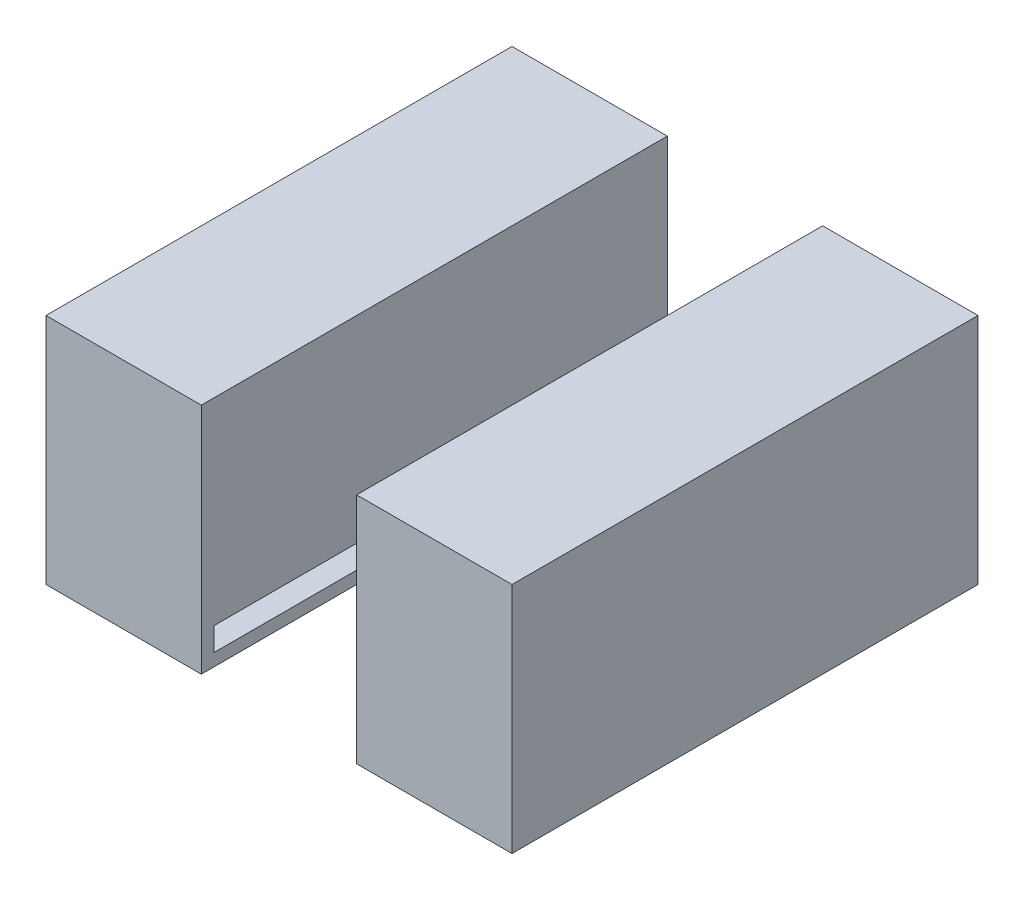
SolidWorks part; units mm, degrees
material "ABS"
ref_plane "Front Plane" through (0, 0, 0) normal (0, 0, 1) x (1, 0, 0)
ref_plane "Top Plane" through (0, 0, 0) normal (0, 1, 0) x (1, 0, 0)
ref_plane "Right Plane" through (0, 0, 0) normal (1, 0, 0) x (0, 0, -1)
sketch "Sketch1" plane through (0, 0, 0) normal (0, 0, 1) x (1, 0, 0)
  line L1 (-30, -15) -> (30, -15)
  line L2 (-30, -15) -> (-30, 15)
  line L3 (-30, 15) -> (30, 15)
  line L4 (30, -15) -> (30, 15)
  line L5 (0, 15) -> (0, -15) construction
  line L6 (-30, 0) -> (30, 0) construction
  point P16 (0, 0)
extrude "Boss-Extrude1" add sketch "Sketch1" along normal mid plane 60
sketch "Sketch2" plane through (0, 0, 0) normal (0, 0, 1) x (1, 0, 0)
  line L0 (-30, -15) -> (30, -15) construction
  line L1 (-10, -15) -> (10, -15)
  line L2 (-10, -15) -> (-10, 15)
  line L3 (-10, 15) -> (10, 15)
  line L4 (10, -15) -> (10, 15)
  line L5 (0, 15) -> (0, -15) construction
  line L6 (-10, 0) -> (10, 0) construction
  line L7 (30, 15) -> (-30, 15) construction
  point P20 (0, 0)
extrude "Cut-Extrude1" cut sketch "Sketch2" against normal mid plane 60
sketch "Sketch3" plane through (0, 0, 0) normal (0, 0, 1) x (1, 0, 0)
  line L1 (-28.4, -13.4) -> (-11.6, -13.4)
  line L2 (-28.4, -13.4) -> (-28.4, 13.4)
  line L3 (-28.4, 13.4) -> (-11.6, 13.4)
  line L4 (-11.6, -13.4) -> (-11.6, 13.4)
  line L5 (-20, 13.4) -> (-20, -13.4) construction
  line L6 (-28.4, 0) -> (-11.6, 0) construction
  line L7 (11.6, -13.4) -> (28.4, -13.4)
  line L8 (11.6, -13.4) -> (11.6, 13.4)
  line L9 (11.6, 13.4) -> (28.4, 13.4)
  line L10 (28.4, -13.4) -> (28.4, 13.4)
  line L11 (20, 13.4) -> (20, -13.4) construction
  line L12 (11.6, 0) -> (28.4, 0) construction
  point P16 (-20, 0)
  point P25 (20, 0)
extrude "Cut-Extrude2" cut sketch "Sketch3" against normal mid plane 56.8
sketch "Sketch4" plane through (0, 0, 0) normal (0, 0, 1) x (1, 0, 0)
  line L1 (-16.2, -13.4) -> (-14.6, -13.4)
  line L2 (-16.2, -13.4) -> (-16.2, 10.4)
  line L3 (-16.2, 10.4) -> (-14.6, 10.4)
  line L4 (-14.6, -13.4) -> (-14.6, 10.4)
  line L5 (-15.4, 10.4) -> (-15.4, -13.4) construction
  line L6 (-16.2, -1.5) -> (-14.6, -1.5) construction
  line L7 (-20.8, -10.4) -> (-19.2, -10.4)
  line L8 (-20.8, -10.4) -> (-20.8, 13.4)
  line L9 (-20.8, 13.4) -> (-19.2, 13.4)
  line L10 (-19.2, -10.4) -> (-19.2, 13.4)
  line L11 (-20, 13.4) -> (-20, -10.4) construction
  line L12 (-20.8, 1.5) -> (-19.2, 1.5) construction
  line L13 (-25.4, -13.4) -> (-23.8, -13.4)
  line L14 (-25.4, -13.4) -> (-25.4, 10.4)
  line L15 (-25.4, 10.4) -> (-23.8, 10.4)
  line L16 (-23.8, -13.4) -> (-23.8, 10.4)
  line L17 (-24.6, 10.4) -> (-24.6, -13.4) construction
  line L18 (-25.4, -1.5) -> (-23.8, -1.5) construction
  line L19 (14.6, -13.4) -> (16.2, -13.4)
  line L20 (14.6, -13.4) -> (14.6, 10.4)
  line L21 (14.6, 10.4) -> (16.2, 10.4)
  line L22 (16.2, -13.4) -> (16.2, 10.4)
  line L23 (15.4, 10.4) -> (15.4, -13.4) construction
  line L24 (14.6, -1.5) -> (16.2, -1.5) construction
  line L25 (19.2, -10.4) -> (20.8, -10.4)
  line L26 (19.2, -10.4) -> (19.2, 13.4)
  line L27 (19.2, 13.4) -> (20.8, 13.4)
  line L28 (20.8, -10.4) -> (20.8, 13.4)
  line L29 (20, 13.4) -> (20, -10.4) construction
  line L30 (19.2, 1.5) -> (20.8, 1.5) construction
  line L31 (23.8, -13.4) -> (25.4, -13.4)
  line L32 (23.8, -13.4) -> (23.8, 10.4)
  line L33 (23.8, 10.4) -> (25.4, 10.4)
  line L34 (25.4, -13.4) -> (25.4, 10.4)
  line L35 (24.6, 10.4) -> (24.6, -13.4) construction
  line L36 (23.8, -1.5) -> (25.4, -1.5) construction
  point P16 (-15.4, -1.5)
  point P25 (-20, 1.5)
  point P34 (-24.6, -1.5)
  point P43 (15.4, -1.5)
  point P52 (20, 1.5)
  point P61 (24.6, -1.5)
extrude "Boss-Extrude2" add sketch "Sketch4" along normal mid plane 56.8
sketch "Sketch5" plane through (0, 0, 0) normal (0, 0, 1) x (1, 0, 0)
  line L0 (-10, 15) -> (-10, -15) construction
  line L1 (-11.6, -13.4) -> (-10, -13.4)
  line L2 (-11.6, -13.4) -> (-11.6, -10.4)
  line L3 (-11.6, -10.4) -> (-10, -10.4)
  line L4 (-10, -13.4) -> (-10, -10.4)
  line L5 (-10.8, -10.4) -> (-10.8, -13.4) construction
  line L6 (-11.6, -11.9) -> (-10, -11.9) construction
  line L7 (10, -15) -> (10, 15) construction
  line L8 (10, -13.4) -> (11.6, -13.4)
  line L9 (10, -13.4) -> (10, -10.4)
  line L10 (10, -10.4) -> (11.6, -10.4)
  line L11 (11.6, -13.4) -> (11.6, -10.4)
  line L12 (10.8, -10.4) -> (10.8, -13.4) construction
  line L13 (10, -11.9) -> (11.6, -11.9) construction
  point P20 (-10.8, -11.9)
  point P27 (10.8, -11.9)
extrude "Cut-Extrude3" cut sketch "Sketch5" against normal mid plane 56.8
equation "\"W_cell\" = 60mm"
equation "\"H_cell\" = 30mm"
equation "\"D_cell\" = 60mm"
equation "\"W_airway\" = 20mm"
equation "\"t_wall\" = 1.6mm"
equation "\"N_passes\" = 4"
equation "\"W_chamber\" = (\"W_cell\" - \"W_airway\") / 2"
equation "\"w_slit\" = (\"W_chamber\" - (\"N_passes\" + 1) * \"t_wall\") / \"N_passes\""
equation "\"L_baffle\" = \"H_cell\" - (2 * \"t_wall\") - \"w_slit\""
equation "\"L_waveguide\" = 100mm"
